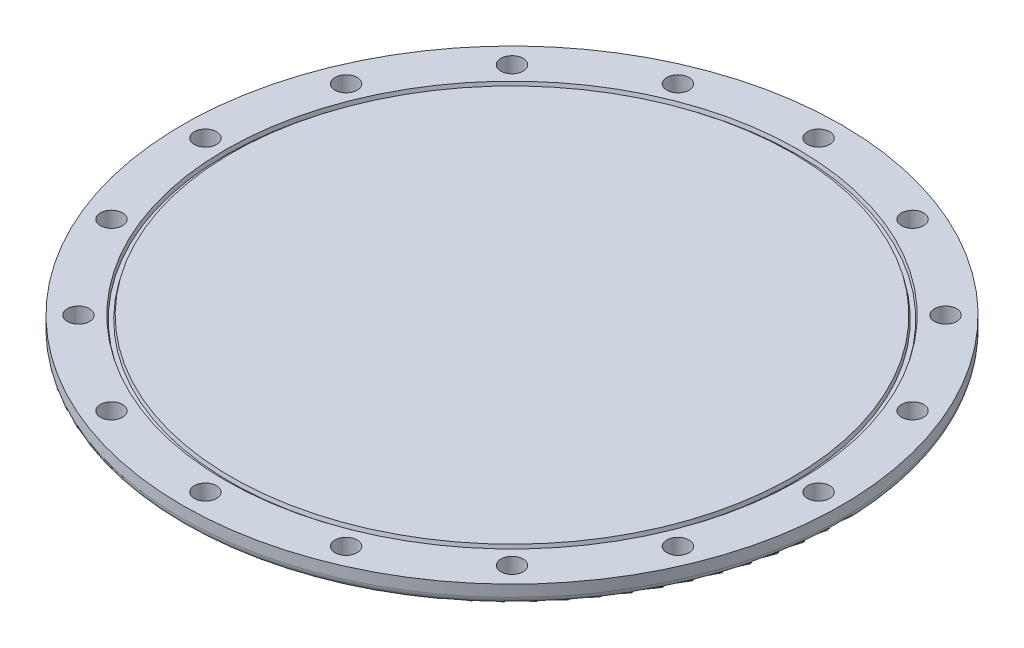
SolidWorks part; units mm, degrees
ref_plane "Front Plane" through (0, 0, 0) normal (0, 0, 1) x (1, 0, 0)
ref_plane "Top Plane" through (0, 0, 0) normal (0, 1, 0) x (1, 0, 0)
ref_plane "Right Plane" through (0, 0, 0) normal (1, 0, 0) x (0, 0, -1)
sketch "Sketch1" plane through (0, 0, 0) normal (0, 1, 0) x (1, 0, 0)
  circle A0 centre (0, 0) radius 86
  dimension "D1" = 172
extrude "Boss-Extrude1" add sketch "Sketch1" along normal blind 5 contours A0
sketch "Sketch2" plane through (0, 5, 0) normal (0, 1, 0) x (1, 0, 0)
  circle A0 centre (0, 0) radius 80 construction
  circle A1 centre (0, 80) radius 2.9
  circle A2 centre (30.6147, 73.9104) radius 2.9
  circle A3 centre (56.5685, 56.5685) radius 2.9
  circle A4 centre (73.9104, 30.6147) radius 2.9
  circle A5 centre (80, 0) radius 2.9
  circle A6 centre (73.9104, -30.6147) radius 2.9
  circle A7 centre (56.5685, -56.5685) radius 2.9
  circle A8 centre (30.6147, -73.9104) radius 2.9
  circle A9 centre (0, -80) radius 2.9
  circle A10 centre (-30.6147, -73.9104) radius 2.9
  circle A11 centre (-56.5685, -56.5685) radius 2.9
  circle A12 centre (-73.9104, -30.6147) radius 2.9
  circle A13 centre (-80, 0) radius 2.9
  circle A14 centre (-73.9104, 30.6147) radius 2.9
  circle A15 centre (-56.5685, 56.5685) radius 2.9
  circle A16 centre (-30.6147, 73.9104) radius 2.9
  point P38 (0, 0)
  dimension "D1" = 160
  dimension "D2" = 5.8
  dimension "D3" = 16
extrude "Cut-Extrude1" cut sketch "Sketch2" against normal up to next
sketch "Sketch4" plane through (0, 0, 0) normal (0, 0, 1) x (1, 0, 0)
  line L0 (0, 0) -> (74, 0) construction
  line L1 (-86, 0) -> (86, 0) construction
  line L2 (74, 0) -> (74, 5) construction
  line L3 (76.8104, 5) -> (71.0104, 5) construction
  line L4 (74, 4) -> (74.5, 4)
  line L5 (74.5, 4) -> (74.7679, 5)
  line L6 (74.7679, 5) -> (73.2321, 5)
  line L7 (73.2321, 5) -> (73.5, 4)
  line L8 (73.5, 4) -> (74, 4)
  line L9 (0, 0) -> (0, 12.8224) construction
  dimension "D1" = 74
  dimension "D2" = 1
  dimension "D3" = 1
  dimension "D4" = 75
revolve "Cut-Revolve1" cut sketch "Sketch4" angle 360 about L9
fillet "Fillet1" radius 2 1 edges at (0, 0, 86)
